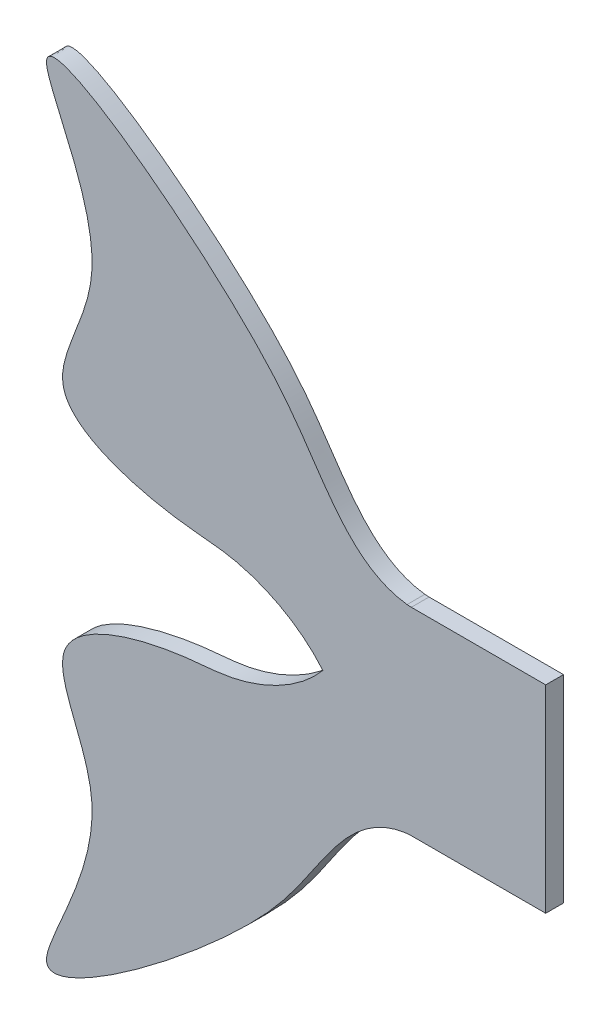
SolidWorks part; units mm, degrees
material "Silicon Rubber"
ref_plane "Front Plane" through (0, 0, 0) normal (0, 0, 1) x (1, 0, 0)
ref_plane "Top Plane" through (0, 0, 0) normal (0, 1, 0) x (1, 0, 0)
ref_plane "Right Plane" through (0, 0, 0) normal (1, 0, 0) x (0, 0, -1)
sketch "Sketch1" plane through (5.5797, 0, 0) normal (0, 0, 1) x (1, 0, 0)
  line L0 (-16.8315, 2.5344) -> (58.4186, 2.5344) construction
  line L1 (35.4186, 19.2344) -> (58.4186, 19.2344)
  line L2 (58.4186, 19.2344) -> (58.4186, -14.1656)
  line L3 (58.4186, -14.1656) -> (35.4186, -14.1656)
  spline S0 degree 3 poles (35.4186, 19.2344) (27.4693, 19.9613) (20.5282, 30.7105) (6.7777, 50.2099) (-40.8001, 85.7568) (-10.993, 43.005) (-30.6548, 18.7796) (-6.9082, 12.2112) (8.3948, 11.542) (16.8959, 7.2144) (20.7936, 2.5344) knots 0 0 0 0 0.125077 0.19256 0.451722 0.613213 0.726081 0.854298 0.895647 1 1 1 1
  spline S1 degree 3 poles (35.4186, -14.1656) (27.4693, -14.8924) (20.5282, -25.6417) (6.7777, -45.1411) (-40.8001, -80.688) (-10.993, -37.9362) (-30.6548, -13.7108) (-6.9082, -7.1424) (8.3948, -6.4732) (16.8959, -2.1456) (20.7936, 2.5344) knots 0 0 0 0 0.125077 0.19256 0.451722 0.613213 0.726081 0.854298 0.895647 1 1 1 1
  point P2 (35.4186, 19.2344)
  point P4 (28.2559, 21.9503)
  point P5 (18.9077, 32.8973)
  point P6 (11.6779, 42.3493)
  point P7 (-25.8369, 68.4476)
  point P8 (-18.2296, 41.0056)
  point P9 (-22.8816, 21.6542)
  point P10 (-19.7018, 51.642)
  point P11 (-2.3396, 12.2089)
  point P12 (4.904, 11.3761)
  point P13 (-11.7109, 14.1078)
  point P14 (11.6827, 9.2633)
  point P15 (20.7936, 2.5344)
  point P18 (23.6553, 26.3422)
  point P33 (-7.4517, 59.5717)
  point P44 (-21.6509, 57.0455)
  point P55 (3.2804, 50.6493)
  point P59 (-15.2763, 15.3484)
  point P63 (-19.1731, -31.2047)
  point P65 (-12.6001, 63.3333)
  point P75 (-24.5075, 69.4436)
  dimension "D2" = 16.7
  dimension "D1" = 60.7989
  dimension "D3" = 23
extrude "Boss-Extrude1" add sketch "Sketch1" along normal mid plane 3
fillet "Fillet1" radius 6 2 edges at (40.9983, 19.2344, 0) (40.9983, -14.1656, 0)
